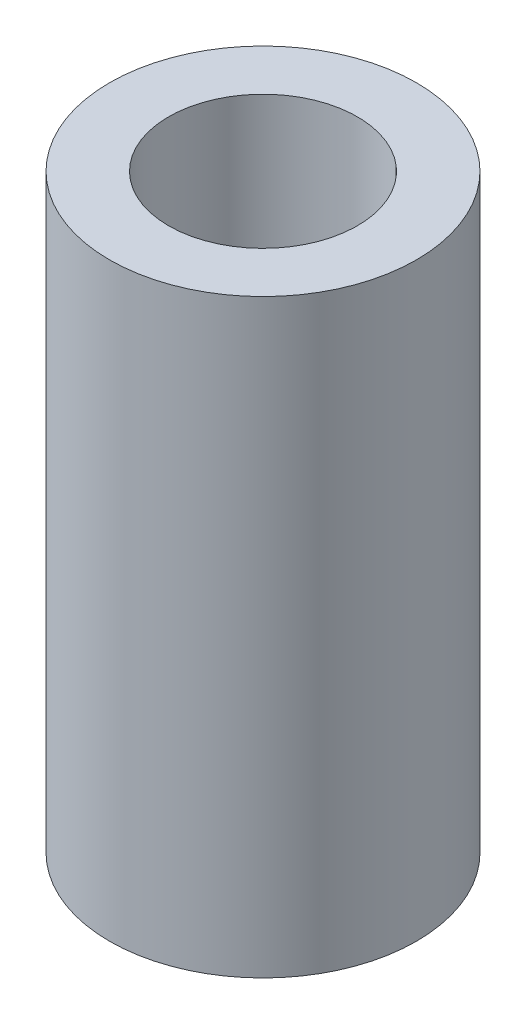
SolidWorks part; units mm, degrees
material "1060 Сплав"
ref_plane "Спереди" through (0, 0, 0) normal (0, 0, 1) x (1, 0, 0)
ref_plane "Сверху" through (0, 0, 0) normal (0, 1, 0) x (1, 0, 0)
ref_plane "Справа" through (0, 0, 0) normal (1, 0, 0) x (0, 0, -1)
sketch "Эскиз1" plane through (0, 0, 0) normal (0, 1, 0) x (1, 0, 0)
  circle A0 centre (0, 0) radius 6.5
  circle A1 centre (0, 0) radius 4
  dimension "D1" = 8
  dimension "D2" = 13
extrude "Бобышка-Вытянуть1" add sketch "Эскиз1" along normal blind 25
